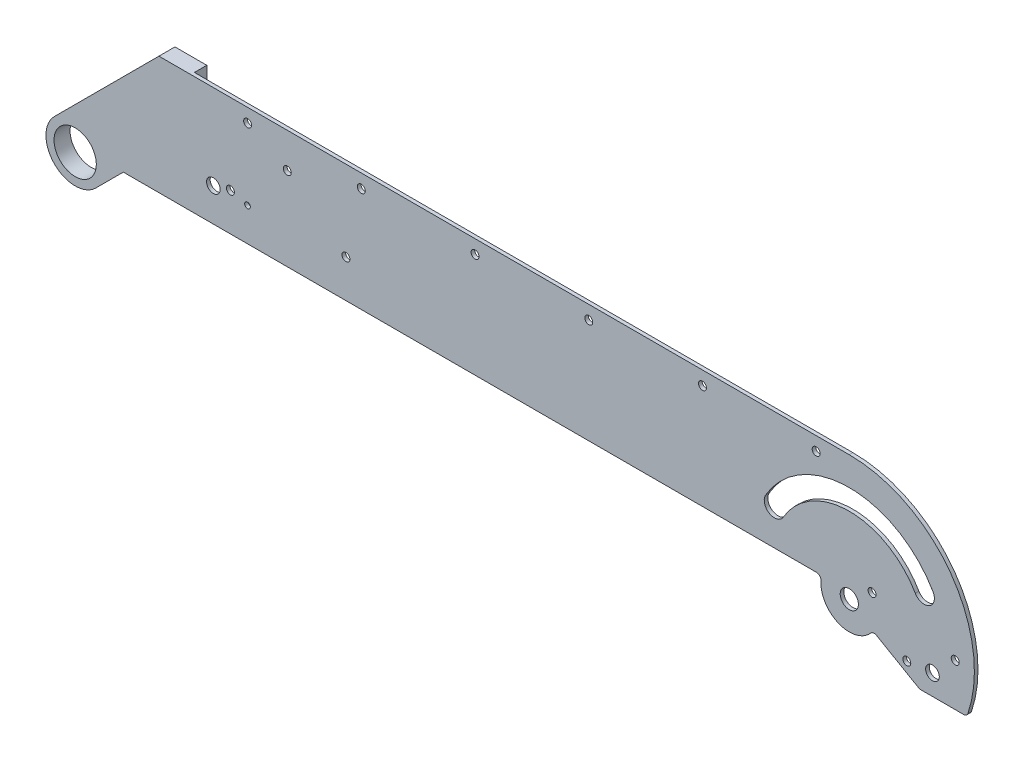
SolidWorks part; units mm, degrees
material "6061-T6 (SS)"
ref_plane "Front Plane" through (0, 0, 0) normal (0, 0, 1) x (1, 0, 0)
ref_plane "Top Plane" through (0, 0, 0) normal (0, 1, 0) x (1, 0, 0)
ref_plane "Right Plane" through (0, 0, 0) normal (1, 0, 0) x (0, 0, -1)
sketch "Sketch1" plane through (0, 0, 0) normal (0, 0, 1) x (1, 0, 0)
  line L0 (0, 0) -> (340.4001, 0) construction
  line L1 (340.4001, 0) -> (373.3091, 19) construction
  line L2 (340.4001, 0) -> (307.4911, 19) construction
  line L3 (340.4001, 0) -> (376.9688, -9.7841) construction
  line L5 (-50, -75) -> (450, -75)
  line L6 (-50, -75) -> (-50, 75)
  line L7 (-50, 75) -> (450, 75)
  line L8 (450, -75) -> (450, 75)
  circle A0 centre (0, 0) radius 9.3
  circle A1 centre (340.4001, 0) radius 4
  circle A2 centre (373.3091, 19) radius 4.5
  circle A3 centre (307.4911, 19) radius 4.5
  circle A4 centre (376.9688, -9.7841) radius 3
  circle A5 centre (340.4001, 0) radius 42.5
  circle A6 centre (340.4001, 0) radius 33.5
  dimension "D1" = 340.4001
  dimension "D2" = 36.5687
  dimension "D6" = 8
  dimension "D7" = 6
  dimension "D8" = 9
  dimension "D9" = 9
  dimension "D12" = 18.6
  dimension "D3" = 9.7841
  dimension "D4" = 150
  dimension "D5" = 120
  dimension "D10" = 38
  dimension "D11" = 38
  dimension "D13" = 150
  dimension "D14" = 500
  dimension "D15" = 75
  dimension "D16" = 50
extrude "Boss-Extrude1" add sketch "Sketch1" along normal blind 1.5875 contours L5 L8 L7 L6 A5 A0 | A6 A3 A5 A2 A4 | A6 A1 region at (189.2496, 0, 0) region at (377.7584, 20.1922, 0) region at (371.8434, 8.4252, 0)
sketch "Sketch3" plane through (0, 0, 1.5875) normal (0, 0, 1) x (1, 0, 0)
  line L0 (-50, 55) -> (450, 55)
  line L1 (340.4001, 0) -> (350.803, -6.9303) construction
  line L2 (-50, -75) -> (-50, 75) construction
  line L3 (450, -75) -> (450, 75) construction
  line L4 (-9.0863, 9.0863) -> (36.8274, 55)
  line L5 (0, 0) -> (-9.0863, 9.0863) construction
  line L6 (0, 0) -> (9.0863, -9.0863) construction
  line L7 (-50, 3) -> (450, 3) construction
  line L8 (9.0863, -9.0863) -> (21.1726, 3)
  line L9 (30.8962, 3) -> (328.2654, 3)
  line L10 (450, -18.7841) -> (-50, -18.7841) construction
  line L11 (350.803, -6.9303) -> (371.3324, -18.7841)
  line L12 (371.3324, -18.7841) -> (392.093, -18.7841)
  line L13 (21.1726, 3) -> (30.8962, 3)
  circle A0 centre (0, 0) radius 12.85
  circle A1 centre (376.9688, -9.7841) radius 3 construction
  circle A2 centre (340.4001, 0) radius 12.5
  circle A3 centre (340.4001, 0) radius 55
  line M7 (-50, -75) -> (450, -75)
  line M8 (450, -75) -> (450, 75)
  line M9 (450, 75) -> (-50, 75)
  line M10 (-50, 75) -> (-50, -75)
  dimension "D1" = 25.7
  dimension "D4" = 9
  dimension "D5" = 25
  dimension "D2" = 55
  dimension "D3" = 3
  dimension "D6" = 23.7059
  dimension "D7" = 149.998
  dimension "D8" = 45
  dimension "D10" = 180
extrude "Cut-Extrude1" cut sketch "Sketch3" against normal blind 7 contours A3 L9 A0 L4 L0 M10 M7 M8 | L9 A3 L12 L11 A2 | L0 M10 M8 M9 region at (200, 65, 1.5875) region at (185.623, -26.8332, 1.5875) region at (333.2112, -26.2581, 1.5875)
sketch "Sketch4" plane through (0, 0, 1.5875) normal (0, 0, 1) x (1, 0, 0)
  line L0 (0, 0) -> (55, 55) construction
  line L1 (36.8274, 55) -> (340.4001, 55) construction
  line L2 (30.8274, 49) -> (6.47, 24.6427)
  line L3 (6.47, 24.6427) -> (23.1127, 8)
  line L4 (-9.0863, 9.0863) -> (36.8274, 55) construction
  line L5 (15.7908, 8) -> (84.2458, 8) construction
  line L6 (21.1726, 3) -> (328.2654, 3) construction
  line L7 (41, 3) -> (41, 8)
  line L8 (23.1127, 8) -> (41, 8)
  line L9 (50.8274, 55) -> (50.8274, 49)
  line L10 (50.8274, 49) -> (30.8274, 49)
  line L11 (50.8274, 55) -> (36.8274, 55)
  line L12 (36.8274, 55) -> (30.8274, 49)
  line L13 (41, 3) -> (21.1726, 3)
  line L14 (21.1726, 3) -> (9.0863, -9.0863)
  line L15 (6.47, 24.6427) -> (-9.0863, 9.0863)
  line L16 (50.8274, 49) -> (41, 8)
  circle A1 centre (0, 0) radius 12.85
  line M7 (36.8274, 55) -> (-9.0863, 9.0863)
  arc M8 (-9.0863, 9.0863) -> (9.0863, -9.0863) centre (0, 0) ccw
  line M9 (9.0863, -9.0863) -> (21.1726, 3)
  line M10 (21.1726, 3) -> (328.2654, 3)
  line M15 (340.4001, 55) -> (36.8274, 55)
  circle M20 centre (0, 0) radius 9.3
  dimension "D1" = 22
  dimension "D2" = 5
  dimension "D3" = 41
  dimension "D4" = 23.5363
  dimension "D5" = 6
  dimension "D6" = 20
extrude "Cut-Extrude2" cut sketch "Sketch4" against normal blind 10 contours A1 L7 L8 L3 M9 M10 M7 | A1 M8 M20 | L10 L9 M15 M7 region at (42.2391, 51.8235, 1.5875) region at (15.8265, 9.8256, 1.5875) region at (4.7784, 11.5361, 1.5875)
fillet "Fillet1" radius 2 3 edges at (392.093, -18.7841, 0.7937) (328.2654, 3, 0.7937) (350.803, -6.9303, 0.7937)
sketch "Sketch5" plane through (0, 0, 1.5875) normal (0, 0, 1) x (1, 0, 0)
  line L0 (6.47, 24.6427) -> (129.4858, 24.6427) construction
  circle A0 centre (17.47, 19.6427) radius 1.75
  circle A1 centre (42.47, 39.6427) radius 1.75
  circle A2 centre (93.27, 39.6427) radius 1.75
  circle A3 centre (68.27, 19.6427) radius 1.75
  circle A4 centre (119.07, 19.6427) radius 1.75
  circle A5 centre (75.77, 17.6427) radius 1.25
  circle A6 centre (60.77, 17.6427) radius 3
  dimension "D1" = 3.5
  dimension "D4" = 3.5
  dimension "D8" = 3.5
  dimension "D9" = 3.5
  dimension "D12" = 3.5
  dimension "D16" = 2.5
  dimension "D17" = 6
  dimension "D2" = 5
  dimension "D3" = 11
  dimension "D5" = 15
  dimension "D6" = 36
  dimension "D7" = 50.8
  dimension "D10" = 50.8
  dimension "D11" = 50.8
  dimension "D13" = 15
  dimension "D14" = 5
  dimension "D15" = 5
  dimension "D18" = 2
  dimension "D19" = 7.5
  dimension "D20" = 7.5
  dimension "D21" = 2
extrude "Cut-Extrude3" cut sketch "Sketch5" against normal blind 10
sketch "Sketch6" plane through (0, 0, 1.5875) normal (0, 0, 1) x (1, 0, 0)
  line L0 (340.4001, 0) -> (395.4001, 0) construction
  line L1 (350.4001, 7.5) -> (386.9688, 0) construction
  line L2 (368.6844, 3.75) -> (364.8326, -15.0311) construction
  line L3 (352.3209, -7.8068) -> (371.3324, -18.7841) construction
  circle A0 centre (340.4001, 0) radius 4
  circle A1 centre (376.9688, -9.7841) radius 3
  arc A2 (392.5694, -17.4175) -> (340.4001, 55) centre (340.4001, 0) ccw construction
  circle A3 centre (350.4001, 7.5) radius 1.75
  circle A4 centre (386.9688, 0) radius 1.75
  circle A5 centre (365.6708, -10.9441) radius 1.75
  dimension "D1" = 3.5
  dimension "D4" = 3.5
  dimension "D6" = 3.5
  dimension "D2" = 7.5
  dimension "D3" = 10
  dimension "D5" = 10
  dimension "D7" = 15
extrude "Cut-Extrude4" cut sketch "Sketch6" against normal blind 10
sketch "Sketch7" plane through (0, 0, 1.5875) normal (0, 0, 1) x (1, 0, 0)
  line L0 (50.8274, 49) -> (340.6, 49) construction
  circle A0 centre (75.8274, 49) radius 1.75
  circle A1 centre (125.8274, 49) radius 1.75
  circle A2 centre (175.8274, 49) radius 1.75
  circle A3 centre (225.8274, 49) radius 1.75
  circle A4 centre (275.8274, 49) radius 1.75
  circle A5 centre (325.8274, 49) radius 1.75
  dimension "D6" = 3.5
  dimension "D7" = 3.5
  dimension "D8" = 3.5
  dimension "D9" = 3.5
  dimension "D10" = 3.5
  dimension "D12" = 3.5
  dimension "D1" = 25
  dimension "D2" = 50
  dimension "D3" = 50
  dimension "D4" = 50
  dimension "D5" = 50
  dimension "D11" = 50
extrude "Cut-Extrude5" cut sketch "Sketch7" against normal blind 246.38
extrude "Boss-Extrude2" add sketch "Sketch4<3>" against normal blind 7.045 contours L10 L9 M15 M7 | A1 L7 L8 L3 M9 M10 M7 | A1 M8 M20 | L16 L10 L3 L8 M7 region at (30.9038, 28.3094, 1.5875) region at (42.2391, 51.8235, 1.5875) region at (15.8265, 9.8256, 1.5875) region at (4.7784, 11.5361, 1.5875)
sketch "Sketch4<3>" plane through (0, 0, 1.5875) normal (0, 0, 1) x (1, 0, 0) same geometry as "Sketch4"
